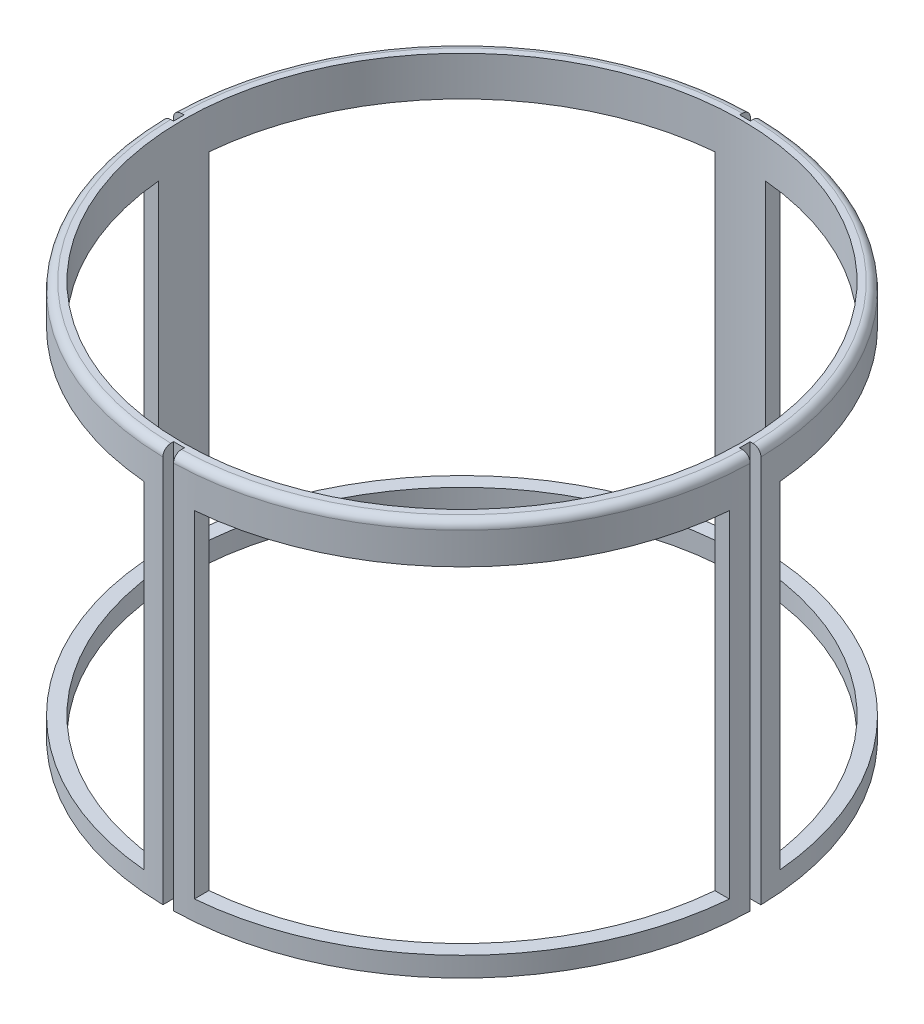
SolidWorks part; units mm, degrees
ref_plane "Front" through (0, 0, 0) normal (0, 0, 1) x (1, 0, 0)
ref_plane "Top" through (0, 0, 0) normal (0, 1, 0) x (1, 0, 0)
ref_plane "Right" through (0, 0, 0) normal (1, 0, 0) x (0, 0, -1)
sketch "Sketch1" plane through (0, 0, 0) normal (0, 1, 0) x (1, 0, 0)
  circle A0 centre (0, 0) radius 89.662
  circle A1 centre (0, 0) radius 94.2975
  dimension "Inner Diameter" = 179.324
  dimension "Outer Diameter" = 188.595
extrude "Boss-Extrude1" add sketch "Sketch1" against normal blind 127
sketch "Sketch5" plane through (0, 0, 0) normal (0, 1, 0) x (1, 0, 0)
  line L0 (0, 114.2751) -> (0, -136.7211) construction
  line L1 (-124.857, 0) -> (116.4345, 0) construction
  line L2 (-1.7145, 90.8209) -> (1.7145, 90.8209)
  line L3 (1.7145, 90.8209) -> (1.7145, 95.9009)
  line L4 (1.7145, 95.9009) -> (-1.7145, 95.9009)
  line L5 (-1.7145, 95.9009) -> (-1.7145, 90.8209)
  line L6 (1.7145, -95.9009) -> (-1.7145, -95.9009)
  line L7 (1.7145, -90.8209) -> (1.7145, -95.9009)
  line L8 (-1.7145, -90.8209) -> (1.7145, -90.8209)
  line L9 (-1.7145, -95.9009) -> (-1.7145, -90.8209)
  line L10 (-90.8209, 1.651) -> (-90.8209, -1.778)
  line L11 (-90.8209, -1.778) -> (-95.9009, -1.778)
  line L12 (-95.9009, -1.778) -> (-95.9009, 1.651)
  line L13 (-95.9009, 1.651) -> (-90.8209, 1.651)
  line L14 (95.9009, -1.778) -> (95.9009, 1.651)
  line L15 (90.8209, -1.778) -> (95.9009, -1.778)
  line L16 (90.8209, 1.651) -> (90.8209, -1.778)
  line L17 (95.9009, 1.651) -> (90.8209, 1.651)
  dimension "D1" = 1.7145
  dimension "D2" = 1.7145
  dimension "D3" = 5.08
  dimension "D4" = 90.8209
  dimension "D5" = 1.651
  dimension "D6" = 90.8209
extrude "Cut-Extrude1" cut sketch "Sketch5" against normal blind 127
sketch "Sketch7" plane through (0, 0, 0) normal (0, 1, 0) x (1, 0, 0)
  line L0 (89.2928, -8.128) -> (93.9465, -8.128)
  line L1 (8.0645, -89.2986) -> (8.0645, -93.952)
  line L2 (1.7145, -94.2819) -> (1.7145, -90.8209) construction
  line L3 (90.8209, -1.778) -> (94.2807, -1.778) construction
  arc A0 (89.2928, -8.128) -> (8.0645, -89.2986) centre (0, 0) cw
  circle A1 centre (0, 0) radius 89.662 construction
  arc A2 (93.9465, -8.128) -> (8.0645, -93.952) centre (0, 0) cw
  arc A3 (1.7145, -94.2819) -> (94.2807, -1.778) centre (0, 0) ccw construction
  point P15 (92.5508, -1.778)
  dimension "D3" = 94.2975
  dimension "D4" = 89.662
  dimension "D1" = 6.35
  dimension "D2" = 6.35
extrude "Cut-Extrude2" cut sketch "Sketch7" against normal blind 107.95 from offset 12.7 offset against normal yes
pattern_circular "CirPattern1" count 4 over 360 about axis through (0, 0, 0) along (0, 1, 0) of "Cut-Extrude2"
fillet "Fillet1" radius 2.54 4 edges at (-66.7009, 0, -66.6559) (66.7009, 0, -66.6559) (66.6559, 0, 66.7009) (-66.6559, 0, 66.7009)
equation "\"D4@Sketch5\"=(\"Inner Diameter\"/2)+((\"Outer Diameter\"-\"Inner Diameter\")/8)"
equation "\"D6@Sketch5\"=(\"Inner Diameter\"/2)+((\"Outer Diameter\"-\"Inner Diameter\")/8)"
equation "\"D1@Cut-Extrude1\"=\"Fin Length\""
equation "\"D3@Sketch7\"=\"Outer Diameter\"/2"
equation "\"D4@Sketch7\"=\"Inner Diameter\"/2"
